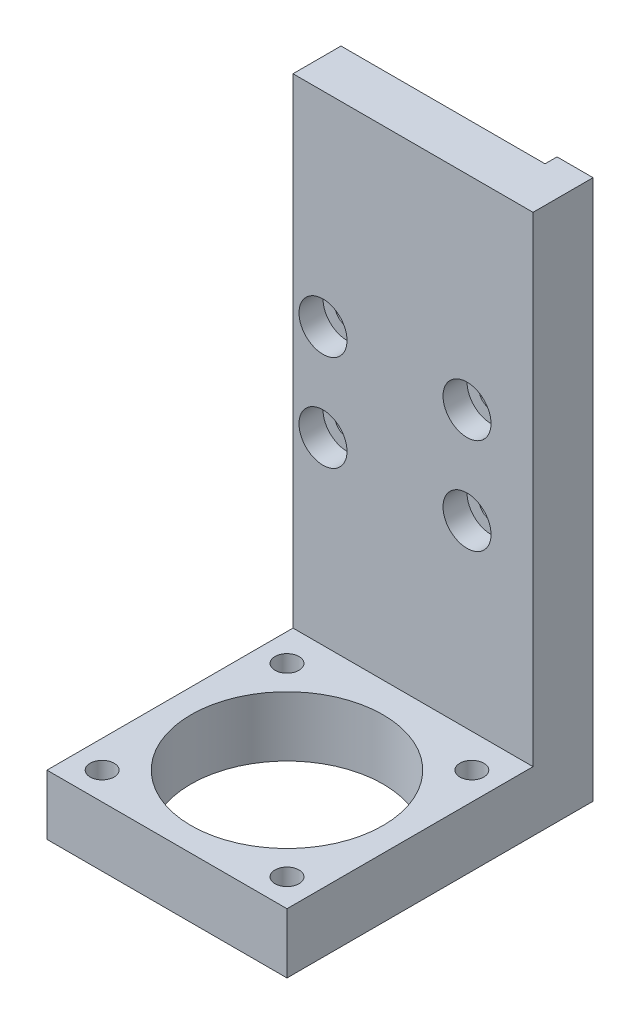
SolidWorks part; units mm, degrees
ref_plane "Front Plane" through (0, 0, 0) normal (0, 0, 1) x (1, 0, 0)
ref_plane "Top Plane" through (0, 0, 0) normal (0, 1, 0) x (1, 0, 0)
ref_plane "Right Plane" through (0, 0, 0) normal (1, 0, 0) x (0, 0, -1)
sketch "Sketch1" plane through (0, 0, 0) normal (1, 0, 0) x (0, 0, -1)
  line L0 (0, 0) -> (20.5, 0)
  line L1 (20.5, 0) -> (20.5, 40)
  line L2 (20.5, 40) -> (25.5, 40)
  line L3 (25.5, 40) -> (25.5, -5)
  line L4 (25.5, -5) -> (0, -5)
  line L5 (0, -5) -> (0, 0)
  dimension "D1" = 20.5
  dimension "D2" = 5
  dimension "D3" = 5
  dimension "D4" = 40
extrude "Boss-Extrude1" add sketch "Sketch1" along normal blind 20
sketch "Sketch3" plane through (0, 0, 0) normal (0, 1, 0) x (1, 0, 0)
  line L0 (20, 20.5) -> (20, 0) construction
  line L1 (20, 0) -> (0, 0) construction
  line L2 (0, 20.5) -> (0, 0) construction
  circle A0 centre (10, 10) radius 8
  circle A1 centre (2.3, 17.7) radius 1
  circle A2 centre (17.7, 17.7) radius 1
  circle A3 centre (17.7, 2.3) radius 1
  circle A4 centre (2.3, 2.3) radius 1
  dimension "D1" = 16
  dimension "D2" = 10
  dimension "D3" = 10
  dimension "D4" = 15.4
  dimension "D5" = 2
  dimension "D6" = 2
  dimension "D7" = 2
  dimension "D8" = 2
  dimension "D9" = 15.4
  dimension "D10" = 15.4
  dimension "D11" = 15.4
  dimension "D12" = 2.3
  dimension "D13" = 2.3
  dimension "D14" = 2.3
  dimension "D15" = 2.3
  dimension "D16" = 2.3
  dimension "D17" = 2.3
extrude "Cut-Extrude1" cut sketch "Sketch3" against normal blind 10
sketch "Sketch4" plane through (0, 0, -20.5) normal (0, 0, 1) x (1, 0, 0)
  line L0 (0, 40) -> (0, 0) construction
  line L1 (20, 0) -> (0, 0) construction
  circle A0 centre (2.5, 15) radius 1
  circle A1 centre (2.5, 23) radius 1
  circle A2 centre (14.5, 23) radius 1
  circle A3 centre (14.5, 15) radius 1
  dimension "D1" = 2
  dimension "D2" = 2
  dimension "D3" = 2
  dimension "D4" = 2
  dimension "D5" = 2.5
  dimension "D6" = 2.5
  dimension "D7" = 12
  dimension "D8" = 12
  dimension "D9" = 8
  dimension "D10" = 8
  dimension "D11" = 0
  dimension "D12" = 15
extrude "Cut-Extrude2" cut sketch "Sketch4" against normal blind 10
sketch "Sketch5" plane through (0, 0, -20.5) normal (0, 0, 1) x (1, 0, 0)
  circle A0 centre (2.5, 23) radius 2
  circle A1 centre (2.5, 15) radius 2
  circle A2 centre (14.5, 15) radius 2
  circle A3 centre (14.5, 23) radius 2
  dimension "D1" = 4
  dimension "D2" = 4
  dimension "D3" = 4
  dimension "D4" = 4
extrude "Cut-Extrude3" cut sketch "Sketch5" against normal blind 2
sketch "Sketch6" plane through (0, 40, 0) normal (0, 1, 0) x (1, 0, 0)
  line L1 (0, 25.5) -> (17, 25.5)
  line L2 (0, 25.5) -> (0, 24.5)
  line L3 (0, 24.5) -> (17, 24.5)
  line L4 (17, 25.5) -> (17, 24.5)
  dimension "D1" = 17
  dimension "D2" = 1
extrude "Cut-Extrude4" cut sketch "Sketch6" against normal blind 65
